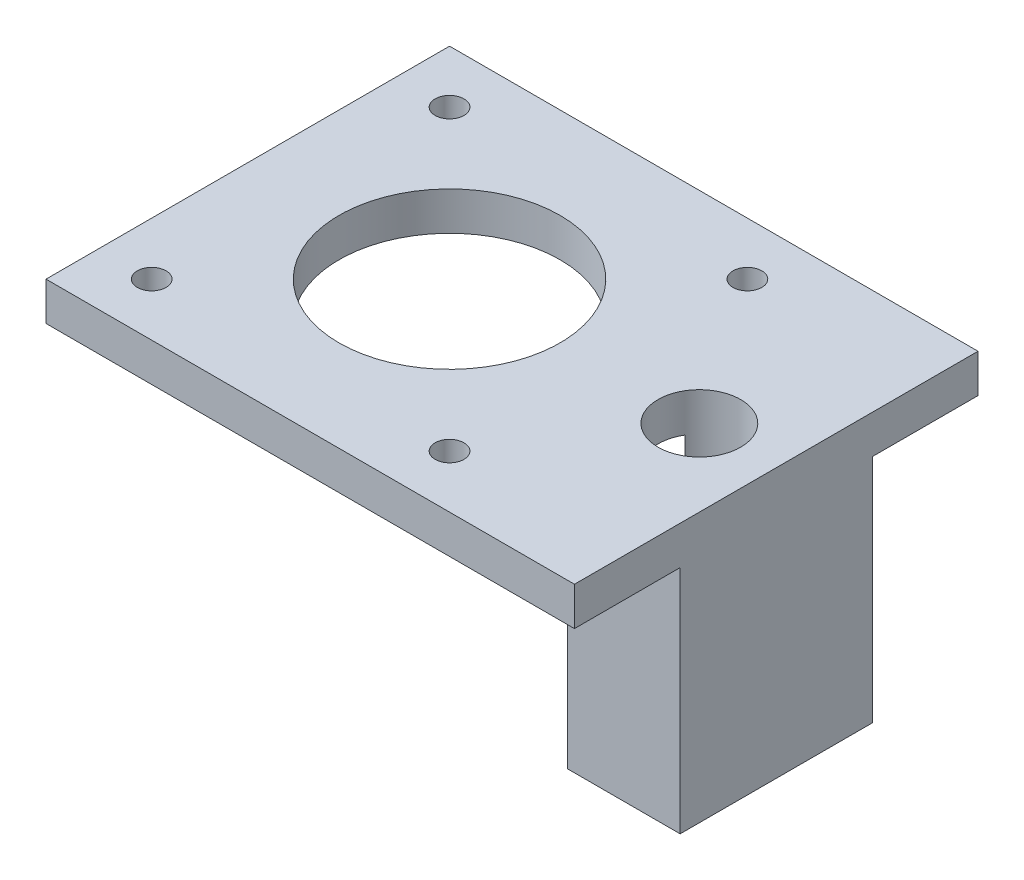
SolidWorks part; units mm, degrees
ref_plane "Front Plane" through (0, 0, 0) normal (0, 0, 1) x (1, 0, 0)
ref_plane "Top Plane" through (0, 0, 0) normal (0, 1, 0) x (1, 0, 0)
ref_plane "Right Plane" through (0, 0, 0) normal (1, 0, 0) x (0, 0, -1)
sketch "Sketch1" plane through (0, 0, 0) normal (0, 1, 0) x (1, 0, 0)
  line L0 (0, 21) -> (55, 21) construction
  line L1 (0, 0) -> (55, 0)
  line L2 (0, 0) -> (0, 42)
  line L3 (0, 42) -> (55, 42)
  line L4 (55, 0) -> (55, 42)
  line L5 (21, 42) -> (21, 0) construction
  circle A0 centre (47, 21) radius 4.3
  circle A1 centre (21, 21) radius 11.5
  circle A2 centre (5.5, 36.5) radius 1.5
  circle A3 centre (36.5, 36.5) radius 1.5
  circle A4 centre (5.5, 5.5) radius 1.5
  circle A5 centre (36.5, 5.5) radius 1.5
  point P8 (55, 21)
  dimension "D2" = 23
  dimension "D4" = 8.6
  dimension "D9" = 3
  dimension "D1" = 26
  dimension "D3" = 42
  dimension "D5" = 21
  dimension "D6" = 55
  dimension "D7" = 15.5
  dimension "D8" = 15.5
extrude "Boss-Extrude1" add sketch "Sketch1" along normal blind 4
sketch "Sketch2" plane through (0, 0, 0) normal (0, -1, 0) x (1, 0, 0)
  line L0 (0, 0) -> (55, 0) construction
  line L1 (40.3, 0) -> (43.3, 0)
  line L2 (40.3, 0) -> (40.3, -42)
  line L3 (40.3, -42) -> (43.3, -42)
  line L4 (43.3, 0) -> (43.3, -42)
  line L5 (55, -42) -> (0, -42) construction
  line L6 (55, 0) -> (55, -42) construction
  line L7 (55, -11) -> (43.3, -11)
  line L8 (55, -11) -> (55, -31)
  line L9 (55, -31) -> (43.3, -31)
  line L10 (43.3, -11) -> (43.3, -31)
  circle A0 centre (47, -21) radius 6.7
  circle A1 centre (47, -21) radius 4.3
  circle A2 centre (47, -21) radius 4.3 construction
  point P25 (55, -21)
  point P26 (55, -21)
  circle M7 centre (47, -21) radius 4.3
  line M10 (55, -42) -> (55, 0)
  dimension "D1" = 2.4
  dimension "D2" = 3
  dimension "D3" = 20
extrude "Boss-Extrude2" add sketch "Sketch2" along normal blind 20 contours L4 A0 L10 M7 | A0 L10 L9 L7 L4 M10 region at (49.15, 0, -11.2317) region at (50.0899, 0, -15.2469)
sketch "Sketch3" plane through (0, -20, 0) normal (0, -1, 0) x (1, 0, 0)
  line L1 (55, -31) -> (43.3, -31)
  line L2 (55, -31) -> (55, -11)
  line L3 (55, -11) -> (43.3, -11)
  line L4 (43.3, -31) -> (43.3, -11)
extrude "Boss-Extrude3" add sketch "Sketch3" along normal blind 4
equation "\"8mm hole\" = 8.6mm"
equation "\"22mm hole\"= 23mm"
equation "\"D2@Sketch1\"=\"22mm hole\""
equation "\"D4@Sketch1\"=\"8mm hole\""
